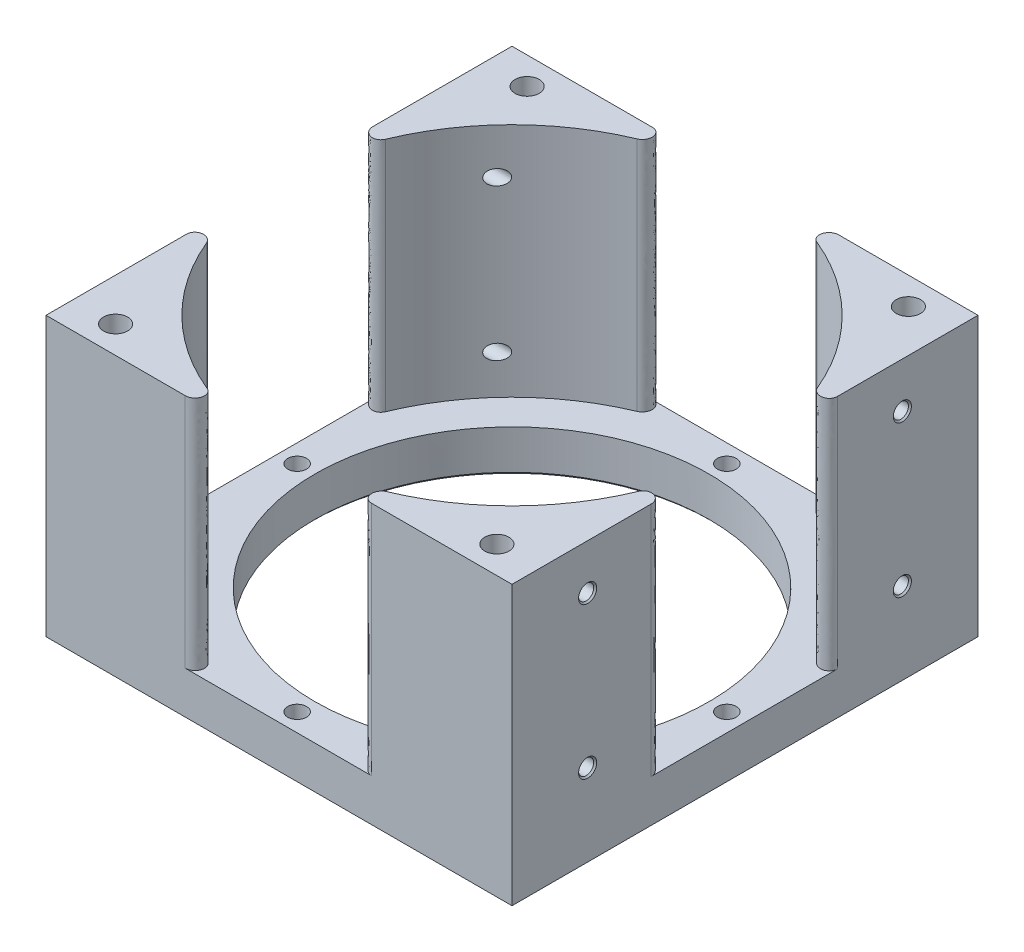
SolidWorks part; units mm, degrees
ref_plane "Ebene vorne" through (0, 0, 0) normal (0, 0, 1) x (1, 0, 0)
ref_plane "Ebene oben" through (0, 0, 0) normal (0, 1, 0) x (1, 0, 0)
ref_plane "Ebene rechts" through (0, 0, 0) normal (1, 0, 0) x (0, 0, -1)
sketch "Skizze1" plane through (0, 0, 0) normal (0, 1, 0) x (1, 0, 0)
  line L1 (-38.5, -38.5) -> (38.5, -38.5)
  line L2 (-38.5, -38.5) -> (-38.5, 38.5)
  line L3 (-38.5, 38.5) -> (38.5, 38.5)
  line L4 (38.5, -38.5) -> (38.5, 38.5)
  line L5 (-38.5, -38.5) -> (38.5, 38.5) construction
  line L6 (-38.5, 38.5) -> (38.5, -38.5) construction
  point P0 (0, 0)
  dimension "D1" = 77
extrude "Aufsatz-Linear austragen1" add sketch "Skizze1" along normal blind 7
sketch "Skizze2" plane through (0, 7, 0) normal (0, 1, 0) x (1, 0, 0)
  line L0 (2.4043, 38.5) -> (38.5, 38.5)
  line L1 (-38.5, -38.5) -> (-2.4043, -38.5)
  line L2 (-38.5, -38.5) -> (-38.5, -2.4043)
  line L3 (-38.5, 38.5) -> (-2.4043, 38.5)
  line L4 (38.5, -38.5) -> (38.5, -2.4043)
  line L5 (-38.5, -38.5) -> (38.5, 38.5) construction
  line L6 (-38.5, 38.5) -> (38.5, -38.5) construction
  line L7 (-38.5, 2.4043) -> (-38.5, 38.5)
  line L8 (2.4043, -38.5) -> (38.5, -38.5)
  line L9 (38.5, 2.4043) -> (38.5, 38.5)
  arc A0 (-2.4043, 38.5) -> (-38.5, 2.4043) centre (0, 0) ccw
  arc A1 (-38.5, -2.4043) -> (-2.4043, -38.5) centre (0, 0) ccw
  arc A2 (2.4043, -38.5) -> (38.5, -2.4043) centre (0, 0) ccw
  arc A3 (38.5, 2.4043) -> (2.4043, 38.5) centre (0, 0) ccw
  dimension "D1" = 77.15
extrude "Aufsatz-Linear austragen2" add sketch "Skizze2" along normal blind 39
fillet "Verrundung1" radius 2 8 edges at (38.5, 26.5, 2.4043) (38.5, 26.5, -2.4043) (2.4043, 26.5, -38.5) (-2.4043, 26.5, -38.5) (-38.5, 26.5, -2.4043) (-38.5, 26.5, 2.4043) (2.4043, 26.5, 38.5) (-2.4043, 26.5, 38.5)
sketch "Skizze3" plane through (0, 7, 0) normal (0, 1, 0) x (1, 0, 0)
  circle A0 centre (0, 0) radius 32.575
  dimension "D1" = 65.15
extrude "Schnitt-Linear austragen1" cut sketch "Skizze3" against normal through all
hole_wizard "Ø3.1 (3.1) Durchmesser Bohrung1" positions "Skizze4" profile "Skizze5" hole size "Ø3.1" standard "DIN"
sketch "Skizze4" plane through (0, 7, 0) normal (0, 1, 0) x (1, 0, 0)
  circle A0 centre (0, 0) radius 35.5 construction
  point P5 (0, 35.5)
  point P14 (35.5, 0)
  point P16 (0, -35.5)
  point P18 (-35.5, 0)
  point P20 (0, 0)
  point P21 (25.1023, 25.1023)
  point P22 (0, 0)
  point P23 (25.1023, -25.1023)
  point P24 (0, 0)
  point P25 (-25.1023, -25.1023)
  point P26 (0, 0)
  point P27 (-25.1023, 25.1023)
  dimension "D1" = 71
  dimension "D2" = 8
sketch "Skizze5" plane through (-35.5, 7, 0) normal (1, 0, 0) x (0, 0, 1)
  line L0 (0, 0) -> (0, 7)
  line L1 (0, 7) -> (1.55, 7)
  line L2 (1.55, 7) -> (1.55, 0)
  line L5 (1.55, 0) -> (0, 0)
  line L11 (0, -6.35) -> (0, 107.95) construction
  dimension "Bohrerdurchmesser" = 3.1
  dimension "Bohrungstiefe" = 7
hole_wizard "Ø2.5 (2.5) Durchmesser Bohrung1" positions "Skizze6" profile "Skizze7" hole size "Ø2.5" standard "DIN"
sketch "Skizze6" plane through (38.5, 0, 0) normal (1, 0, 0) x (0, 0, -1)
  line L0 (26, 46) -> (26, -4.5748) construction
  line L1 (15.2948, 46) -> (38.5, 46) construction
  line L2 (0, 0) -> (0, -50000) construction
  point P7 (26, 38.5)
  point P9 (26, 13.5)
  point P16 (-26, 13.5)
  point P17 (-26, 38.5)
  dimension "D1" = 25
  dimension "D2" = 7.5
  dimension "D3" = 26
sketch "Skizze7" plane through (38.5, 38.5, 26) normal (0, 1, 0) x (0, 0, -1)
  line L0 (0, 0) -> (0, 15.7511)
  line L1 (0, 15.7511) -> (1.25, 15)
  line L2 (1.25, 15) -> (1.25, 0.25)
  line L3 (1.25, 0.25) -> (1.5, 0)
  line L5 (1.5, 0) -> (0, 0)
  line L6 (-1.25, 0.25) -> (-1.5, 0) construction
  line L10 (0, 15.7511) -> (-1.25, 15) construction
  line L11 (0, -6.35) -> (0, 107.95) construction
  dimension "Bohrerdurchmesser" = 2.5
  dimension "Bohrungstiefe" = 15
  dimension "Senkdurchmesser2 (Oben)" = 3
  dimension "Senkwinkel2 (Oben)" = 90
  dimension "Spitzenwinkel" = 118
mirror "Spiegeln1" about plane through (0, 0, 0) normal (1, 0, 0) of "Ø2.5 (2.5) Durchmesser Bohrung1"
sketch "Skizze8" plane through (0, 46, 0) normal (0, 1, 0) x (1, 0, 0)
  line L6 (-38.5, 38.5) -> (-38.5, 15.4945) construction
  line L8 (-15.2948, 38.5) -> (-38.5, 38.5) construction
  line L9 (0, 0) -> (0, 50000) construction
  line L10 (0, 0) -> (-50000, 0) construction
  circle A0 centre (-31.5, 34) radius 2
  circle A1 centre (31.5, 34) radius 2
  circle A2 centre (31.5, -34) radius 2
  circle A3 centre (-31.5, -34) radius 2
  dimension "D1" = 4
  dimension "D2" = 5
  dimension "D3" = 2.5
extrude "Schnitt-Linear austragen2" cut sketch "Skizze8" against normal through all
chamfer "Fase1" distance 0.5 angle 45 1 edges at (0, 0, 32.575)
